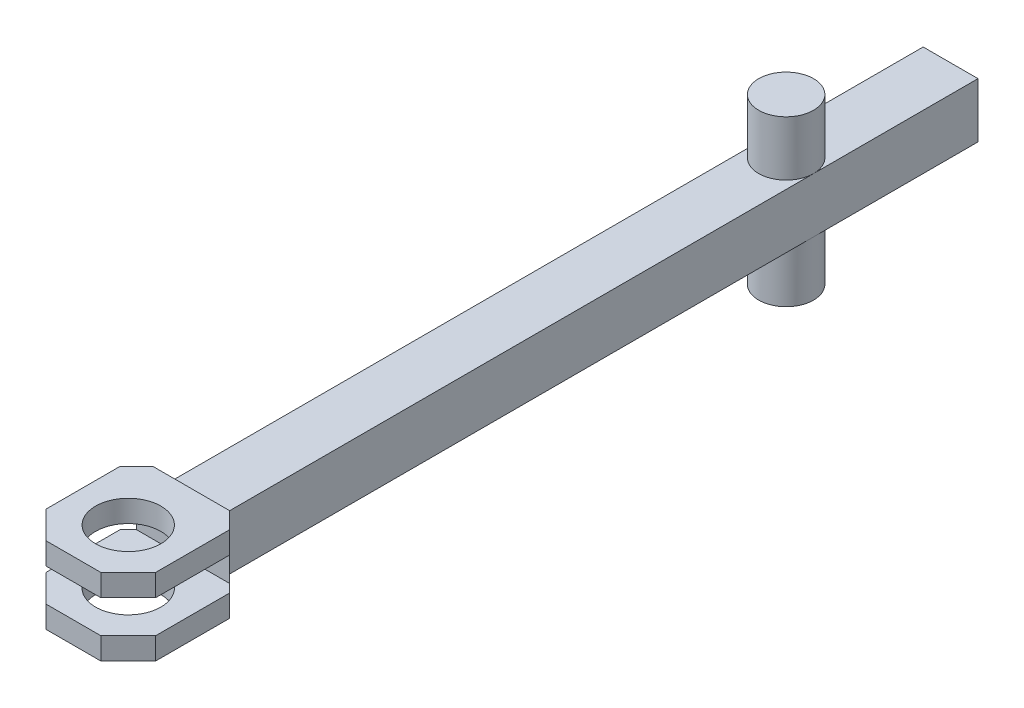
SolidWorks part; units mm, degrees
ref_plane "Front Plane" through (0, 0, 0) normal (0, 0, 1) x (1, 0, 0)
ref_plane "Top Plane" through (0, 0, 0) normal (0, 1, 0) x (1, 0, 0)
ref_plane "Right Plane" through (0, 0, 0) normal (1, 0, 0) x (0, 0, -1)
sketch "Sketch1" plane through (0, 0, 0) normal (0, 0, 1) x (1, 0, 0)
  line L1 (0, 0) -> (100, 0)
  line L2 (0, 0) -> (0, -100)
  line L3 (0, -100) -> (100, -100)
  line L4 (100, 0) -> (100, -100)
  dimension "D1" = 100
  dimension "D2" = 100
extrude "Boss-Extrude1" add sketch "Sketch1" along normal blind 1600
sketch "Sketch2" plane through (0, -100, 0) normal (0, -1, 0) x (1, 0, 0)
  line L0 (100, 1600) -> (100, 0) construction
  line L1 (0, 0) -> (100, 0) construction
  circle A0 centre (50, 300) radius 50
  dimension "D1" = 100
  dimension "D3" = 300
  dimension "D2" = 50
extrude "Boss-Extrude2" add sketch "Sketch2" along normal blind 100 and the other way blind 200
sketch "Sketch4" plane through (0, 0, 0) normal (0, 1, 0) x (1, 0, 0)
  line L0 (100, -1600) -> (0, -1600) construction
  line L1 (-50, -1600) -> (150, -1600)
  line L2 (-50, -1600) -> (-50, -1365.0257)
  line L3 (-50, -1365.0257) -> (150, -1365.0257)
  line L4 (150, -1600) -> (150, -1365.0257)
  line L5 (0, -1600) -> (0, -300) construction
  dimension "D1" = 0
  dimension "D2" = 200
  dimension "D3" = 50
extrude "Boss-Extrude3" add sketch "Sketch4" against normal blind 120 and the other way blind 20
chamfer "Chamfer1" distance 20 angle 45 2 edges at (50, 20, 1365.0257) (50, -120, 1365.0257)
chamfer "Chamfer2" distance 50 angle 45 4 edges at (150, -50, 1365.0257) (-50, -50, 1365.0257) (150, -50, 1600) (-50, -50, 1600)
sketch "Sketch5" plane through (0, -120, 0) normal (0, -1, 0) x (1, 0, 0)
  line L0 (150, 1550) -> (150, 1415.0257) construction
  line L1 (0, 1600) -> (100, 1600) construction
  circle A0 centre (50, 1500) radius 59.5828
  dimension "D1" = 100
  dimension "D2" = 100
extrude "Cut-Extrude2" cut sketch "Sketch5" against normal blind 560
sketch "Sketch6" plane through (0, 0, 1600) normal (0, 0, 1) x (1, 0, 0)
  line L0 (-50, 20) -> (0, 20) construction
  line L1 (-172.4557, -20) -> (277.2312, -20)
  line L2 (-172.4557, -20) -> (-172.4557, -80)
  line L3 (-172.4557, -80) -> (277.2312, -80)
  line L4 (277.2312, -20) -> (277.2312, -80)
  line L5 (0, -120) -> (-50, -120) construction
  dimension "D1" = 40
  dimension "D2" = 40
extrude "Cut-Extrude3" cut sketch "Sketch6" against normal blind 200
